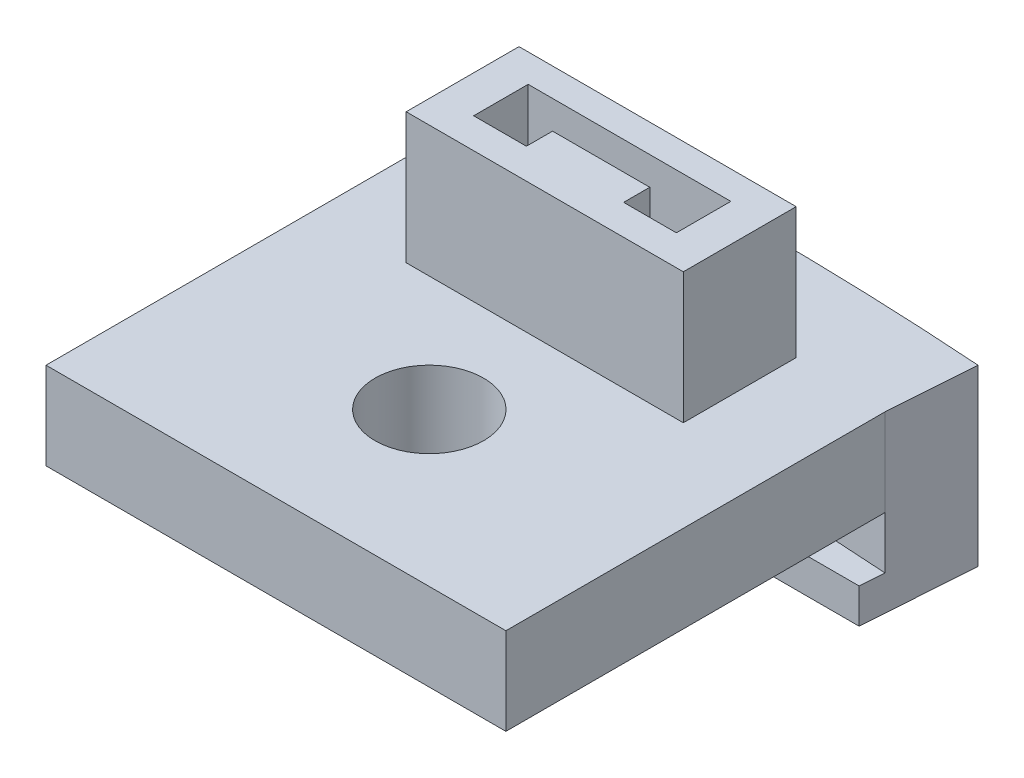
SolidWorks part; units mm, degrees
ref_plane "Front Plane" through (0, 0, 0) normal (0, 0, 1) x (1, 0, 0)
ref_plane "Top Plane" through (0, 0, 0) normal (0, 1, 0) x (1, 0, 0)
ref_plane "Right Plane" through (0, 0, 0) normal (1, 0, 0) x (0, 0, -1)
sketch "Sketch1" plane through (0, 0, 0) normal (0, 1, 0) x (1, 0, 0)
  line L0 (0, 0) -> (0, -3.6068) construction
  line L1 (-5.9055, -5.1308) -> (0, -5.1308)
  line L2 (-5.9055, -1.9558) -> (5.9055, -1.9558)
  line L3 (-13.7536, 4.5978) -> (-13.3993, -0.4679)
  line L4 (13.7536, 4.5978) -> (13.3993, -0.4679)
  line L5 (-5.9055, -1.9558) -> (-5.9055, -5.1308)
  line L6 (0, -5.1308) -> (5.9055, -5.1308)
  line L7 (5.9055, -1.9558) -> (5.9055, -5.1308)
  line L8 (0, -3.6068) -> (-2.8321, -3.6068)
  line L9 (-8.0751, -0.3194) -> (8.0751, -0.3194)
  line L10 (-8.0751, -0.3194) -> (-8.0751, -6.8942)
  line L11 (-2.8321, -3.6068) -> (-2.8321, -5.1308)
  line L12 (0, -3.6068) -> (2.8321, -3.6068)
  line L13 (0, 0) -> (0, -13.6207) construction
  line L14 (-8.0751, -6.8942) -> (8.0751, -6.8942)
  line L15 (2.8321, -3.6068) -> (2.8321, -5.1308)
  line L16 (-13.3993, -0.4679) -> (-13.3993, -22.557)
  line L17 (-13.3993, -22.557) -> (13.3993, -22.557)
  line L18 (13.3993, -0.4679) -> (13.3993, -22.557)
  line L19 (8.0751, -0.3194) -> (8.0751, -6.8942)
  arc A0 (0, 0) -> (13.3993, -0.4679) centre (0, -192.0875) cw
  arc A1 (0, 0) -> (-13.3993, -0.4679) centre (0, -192.0875) ccw
  arc A2 (-13.7536, 4.5978) -> (13.7536, 4.5978) centre (0, -192.0875) cw
  circle A3 centre (0, -13.6207) radius 3.1623
  circle A4 centre (0, -13.6207) radius 5.5308
  dimension "D1" = 11.811
  dimension "D2" = 3.175
extrude "Boss-Extrude1" add sketch "Sketch1" along normal blind 5.08 contours A0 A1 L16 L17 L18 A4 L2 L7 L5 | A4 A3 | A2 L3 A1 A0 L4 | L19 L9 L10 L14 L2 L7 L5 | L18 L16 L17 A4 | A0 A1 L16 L18 L9 L19 L14 L10 region at (0, 0, -2.392) region at (-6.7025, 0, 0.152) region at (0, 0, 0.4938) region at (-5.3744, 0, 13.6207)
extrude "Boss-Extrude2" add sketch "Sketch1<3>" along normal blind 12.7 contours L19 L9 L10 L14 L2 L7 L5 | L15 L12 L8 L11 L1 L6 region at (0, 0, 4.3688) region at (0, 0, 0.4938)
sketch "Sketch1<3>" plane through (0, 0, 0) normal (0, 1, 0) x (1, 0, 0) same geometry as "Sketch1"
extrude "Boss-Extrude3" add sketch "Sketch1<4>" against normal blind 5.08 contours A2 L3 A1 A0 L4 region at (0, 0, -2.392)
sketch "Sketch1<4>" plane through (0, 0, 0) normal (0, 1, 0) x (1, 0, 0) same geometry as "Sketch1"
sketch "Sketch2" plane through (0, -5.08, 0) normal (0, -1, 0) x (1, 0, 0)
  line L0 (-13.7536, -4.5978) -> (-13.3993, 0.4679)
  line L1 (-13.3993, 0.4679) -> (-13.3007, 1.879)
  line L2 (13.7536, -4.5978) -> (13.3993, 0.4679)
  line L3 (13.7536, -4.5978) -> (-13.7536, -4.5978)
  line L4 (13.3993, 0.4679) -> (13.3007, 1.879)
  line L5 (-13.3007, 1.879) -> (13.3007, 1.879)
extrude "Boss-Extrude5" add sketch "Sketch2" against normal blind 2.032
extrude "Boss-Extrude6" add sketch "Sketch1<6>" against normal blind 1.27 contours A4 A3 region at (-5.3744, 0, 13.6207)
sketch "Sketch1<6>" plane through (0, 0, 0) normal (0, 1, 0) x (1, 0, 0) same geometry as "Sketch1"
sketch "Sketch3" plane through (0, 0, 0.3194) normal (0, 0, -1) x (-1, 0, 0)
  circle A0 centre (0, 12.7) radius 2.794
